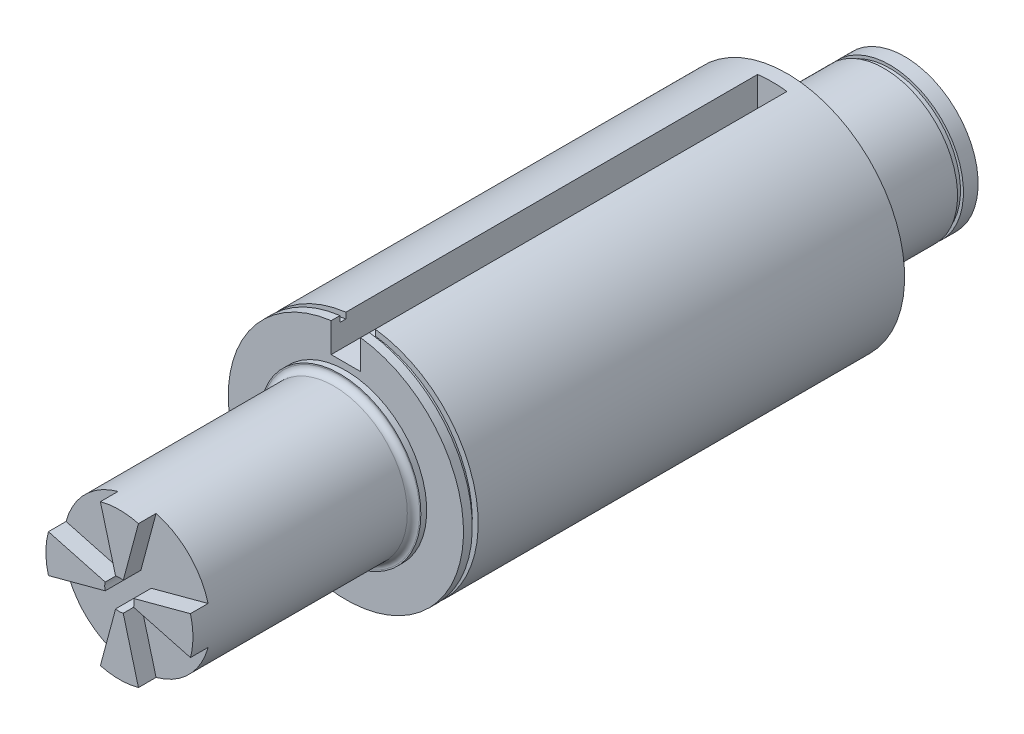
SolidWorks part; units mm, degrees
ref_plane "Plan de face" through (0, 0, 0) normal (0, 0, 1) x (1, 0, 0)
ref_plane "Plan de dessus" through (0, 0, 0) normal (0, 1, 0) x (1, 0, 0)
ref_plane "Plan de droite" through (0, 0, 0) normal (1, 0, 0) x (0, 0, -1)
sketch "Esquisse1" plane through (0, 0, 0) normal (0, 0, 1) x (1, 0, 0)
  circle A0 centre (0, 0) radius 25
  dimension "D1" = 50
extrude "Boss.-Extru.1" add sketch "Esquisse1" against normal blind 100
sketch "Esquisse4" plane through (0, 0, -100) normal (0, 0, -1) x (-1, 0, 0)
  line L0 (0, -1000) -> (0, 29.6863) construction
  line L2 (-5, -957.1075) -> (-5, 49042.8925) construction
  line L3 (5, -954.8323) -> (5, 49045.1677) construction
  line L4 (-5, 39.6863) -> (-5, 29.6863)
  line L5 (-5, 29.6863) -> (5, 29.6863)
  line L6 (5, 29.6863) -> (5, 39.6863)
  arc A0 (-5, 39.6863) -> (5, 39.6863) centre (0, 0) ccw
  point P10 (-5, 39.6863)
  point P12 (5, 39.6863)
  dimension "D1" = 80
  dimension "D3" = 5
  dimension "D4" = 5
  dimension "D5" = 10
extrude "Boss.-Extru.3" add sketch "Esquisse4" along normal blind 150
sketch "Esquisse5" plane through (0, 0, -250) normal (0, 0, -1) x (-1, 0, 0)
  circle A0 centre (0, 0) radius 25
  dimension "D1" = 50
extrude "Boss.-Extru.4" add sketch "Esquisse5" along normal blind 40
sketch "Esquisse6" plane through (0, 0, -100) normal (0, 0, 1) x (1, 0, 0)
  circle A0 centre (0, 0) radius 27.5
  dimension "D1" = 55
extrude "Boss.-Extru.5" add sketch "Esquisse6" along normal blind 2
fillet "Congé2" radius 2.1 1 edges at (25, 0, -98)
ref_plane "Plan1" through (0, 0, -175) normal (0, 0, 1) x (1, 0, 0)
mirror "Symétrie3" about plane through (0, 0, -175) normal (0, 0, 1) of "Boss.-Extru.5"
fillet "Congé3" radius 2.1 1 edges at (-25, 0, -252)
ref_plane "Plan2" through (0, 0, -283) normal (0, 0, -1) x (-1, 0, 0)
sketch "Esquisse7" plane through (0, 0, -283) normal (0, 0, -1) x (-1, 0, 0)
  circle A0 centre (0, 0) radius 25
  circle A1 centre (0, 0) radius 24
  dimension "D1" = 50
  dimension "D2" = 48
extrude "Enlèv. mat.-Extru.1" cut sketch "Esquisse7" along normal blind 2
sketch "Esquisse9" plane through (0, 0, -250) normal (0, 0, -1) x (-1, 0, 0)
  line L0 (-5, 39.6863) -> (-5, 29.6863)
  line L1 (-5, 29.6863) -> (5, 29.6863)
  line L2 (5, 29.6863) -> (5, 39.6863)
  arc A0 (-5, 39.6863) -> (5, 39.6863) centre (0, 0) cw
  arc A1 (-5, 39.6863) -> (5, 39.6863) centre (0, 0) ccw construction
  line M3 (5, 39.6863) -> (5, 29.6863)
  line M4 (5, 29.6863) -> (-5, 29.6863)
  line M5 (-5, 29.6863) -> (-5, 39.6863)
extrude "Boss.-Extru.6" add sketch "Esquisse9" against normal blind 5 contours A0 M5 M4 M3 region at (0, 34.7914, -250)
ref_plane "Plan3" through (0, 0, -105) normal (0, 0, 1) x (1, 0, 0)
sketch "Esquisse10" plane through (0, 0, -105) normal (0, 0, 1) x (1, 0, 0)
  circle A0 centre (0, 0) radius 40
  circle A1 centre (0, 0) radius 38
  dimension "D1" = 76
extrude "Enlèv. mat.-Extru.2" cut sketch "Esquisse10" along normal blind 2
sketch "Esquisse11" plane through (0, 29.6863, 0) normal (0, 1, 0) x (1, 0, 0)
  line L0 (-5, 100) -> (-5, 22.79) construction
  line L1 (-1005, 22.79) -> (48995, 22.79) construction
  line L3 (-25, 95.9) -> (-25, 0) construction
  line L5 (25, 0) -> (-25, 0)
  line L6 (-25, 0) -> (-25, 22.79)
  line L7 (25, 0) -> (25, 22.79)
  line L8 (25, 22.79) -> (-25, 22.79)
  dimension "D1" = 77.21
ref_plane "Plan4" through (0, 0, -22.79) normal (0, 0, 1) x (1, 0, 0)
sketch "Esquisse14" plane through (0, 0, 0) normal (0, 0, 1) x (1, 0, 0)
  line L2 (-6.4705, 24.1481) -> (-1.2941, 4.8296)
  line L9 (1.2941, 4.8296) -> (6.4705, 24.1481)
  line L10 (0, 5) -> (0, 16.0655) construction
  arc A6 (-6.4705, 24.1481) -> (6.4705, 24.1481) centre (0, 0) cw
  circle A7 centre (0, 0) radius 25 construction
  arc A8 (-1.2941, 4.8296) -> (1.2941, 4.8296) centre (0, 0) cw
  dimension "D1" = 30
  dimension "D2" = 15
  dimension "D3" = 20
extrude "Enlèv. mat.-Extru.4" cut sketch "Esquisse14" against normal blind 23
ref_axis "Axe1" through (0, 0, 0) along (0, 0, -1)
pattern_circular "Répétition circulaire2" count 4 over 360 about axis through (0, 0, 0) along (0, 0, -1) of "Enlèv. mat.-Extru.4"
sketch "Esquisse15" plane through (0, 0, 0) normal (0, 0, 1) x (1, 0, 0)
  line L0 (1.2941, 4.8296) -> (6.4705, 24.1481)
  line L1 (-1.2941, 4.8296) -> (-6.4705, 24.1481)
  line L2 (-24.1481, 6.4705) -> (-4.8296, 1.2941)
  line L3 (1.2941, 4.8296) -> (6.4705, 24.1481) construction
  line L4 (4.8296, 1.2941) -> (24.1481, 6.4705)
  line L5 (4.8296, -1.2941) -> (24.1481, -6.4705)
  line L6 (4.8296, -1.2941) -> (24.1481, -6.4705) construction
  line L7 (1.2941, -4.8296) -> (6.4705, -24.1481)
  line L8 (-1.2941, -4.8296) -> (-6.4705, -24.1481)
  line L9 (-4.8296, -1.2941) -> (-24.1481, -6.4705)
  arc A0 (-1.2941, 4.8296) -> (1.2941, 4.8296) centre (0, 0) cw
  arc A1 (-1.2941, -4.8296) -> (1.2941, -4.8296) centre (0, 0) ccw
  arc A2 (1.2941, 4.8296) -> (-1.2941, 4.8296) centre (0, 0) ccw construction
  arc A3 (-6.4705, 24.1481) -> (-24.1481, 6.4705) centre (0, 0) ccw
  arc A4 (-24.1481, 6.4705) -> (-24.1481, -6.4705) centre (0, 0) ccw construction
  arc A5 (-6.4705, 24.1481) -> (-24.1481, 6.4705) centre (0, 0) ccw
  arc A6 (24.1481, 6.4705) -> (6.4705, 24.1481) centre (0, 0) ccw
  arc A7 (6.4705, -24.1481) -> (24.1481, -6.4705) centre (0, 0) ccw
  arc A8 (-24.1481, -6.4705) -> (-6.4705, -24.1481) centre (0, 0) ccw
  arc A9 (-4.8296, 1.2941) -> (-4.8296, -1.2941) centre (0, 0) ccw
  arc A10 (1.2941, 4.8296) -> (-1.2941, 4.8296) centre (0, 0) ccw
  arc A11 (4.8296, -1.2941) -> (4.8296, 1.2941) centre (0, 0) ccw
  line M1 (-6.4705, -24.1481) -> (-1.2941, -4.8296)
  arc M2 (-1.2941, -4.8296) -> (1.2941, -4.8296) centre (0, 0) ccw
  line M3 (1.2941, -4.8296) -> (6.4705, -24.1481)
  arc M4 (6.4705, -24.1481) -> (24.1481, -6.4705) centre (0, 0) ccw
  line M5 (24.1481, -6.4705) -> (4.8296, -1.2941)
  arc M6 (4.8296, -1.2941) -> (4.8296, 1.2941) centre (0, 0) ccw
  line M7 (4.8296, 1.2941) -> (24.1481, 6.4705)
  arc M8 (24.1481, 6.4705) -> (6.4705, 24.1481) centre (0, 0) ccw
  line M9 (6.4705, 24.1481) -> (1.2941, 4.8296)
  arc M10 (1.2941, 4.8296) -> (-1.2941, 4.8296) centre (0, 0) ccw
  line M11 (-1.2941, 4.8296) -> (-6.4705, 24.1481)
  arc M12 (-6.4705, 24.1481) -> (-24.1481, 6.4705) centre (0, 0) ccw
  line M13 (-24.1481, 6.4705) -> (-4.8296, 1.2941)
  arc M14 (-4.8296, 1.2941) -> (-4.8296, -1.2941) centre (0, 0) ccw
  line M15 (-4.8296, -1.2941) -> (-24.1481, -6.4705)
  arc M16 (-24.1481, -6.4705) -> (-6.4705, -24.1481) centre (0, 0) ccw
  dimension "D1" = 10
extrude "Enlèv. mat.-Extru.5" cut sketch "Esquisse15" against normal blind 29 contours M16 M1 M2 M3 M4 M5 M6 M7 M8 M9 M10 M11 M12 M13 M14 M15 region at (0, 0, 0)
